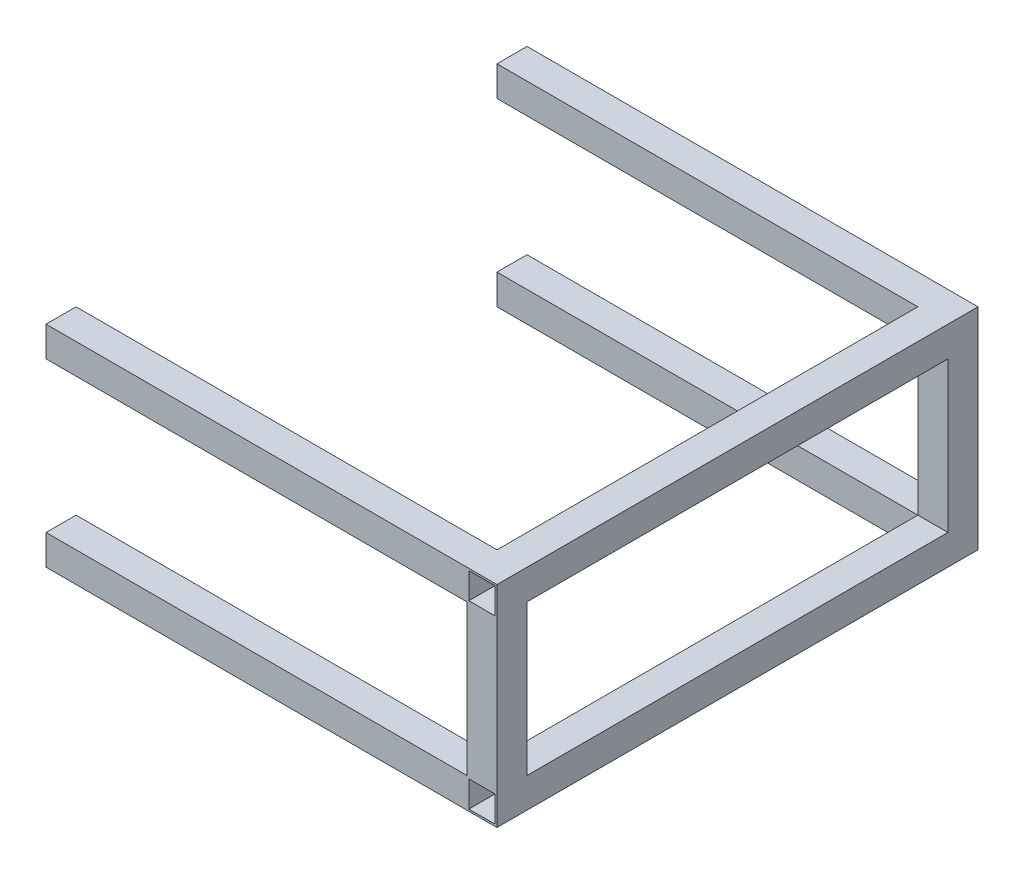
SolidWorks part; units mm, degrees
material "Plain Carbon Steel"
ref_plane "Front Plane" through (0, 0, 0) normal (0, 0, 1) x (1, 0, 0)
ref_plane "Top Plane" through (0, 0, 0) normal (0, 1, 0) x (1, 0, 0)
ref_plane "Right Plane" through (0, 0, 0) normal (1, 0, 0) x (0, 0, -1)
sketch "Sketch1" plane through (0, 0, 0) normal (1, 0, 0) x (0, 0, -1)
  line L1 (-203.2, 88.9) -> (-177.8, 88.9)
  line L2 (-203.2, 88.9) -> (-203.2, 63.5)
  line L3 (-203.2, 63.5) -> (-177.8, 63.5)
  line L4 (-177.8, 88.9) -> (-177.8, 63.5)
  line L5 (-203.2, 88.9) -> (-177.8, 63.5) construction
  line L6 (-203.2, 63.5) -> (-177.8, 88.9) construction
  line L7 (177.8, 88.9) -> (203.2, 88.9)
  line L8 (177.8, 88.9) -> (177.8, 63.5)
  line L9 (177.8, 63.5) -> (203.2, 63.5)
  line L10 (203.2, 88.9) -> (203.2, 63.5)
  line L11 (177.8, 88.9) -> (203.2, 63.5) construction
  line L12 (177.8, 63.5) -> (203.2, 88.9) construction
  line L13 (177.8, -63.5) -> (203.2, -63.5)
  line L14 (177.8, -63.5) -> (177.8, -88.9)
  line L15 (177.8, -88.9) -> (203.2, -88.9)
  line L16 (203.2, -63.5) -> (203.2, -88.9)
  line L17 (177.8, -63.5) -> (203.2, -88.9) construction
  line L18 (177.8, -88.9) -> (203.2, -63.5) construction
  line L19 (-177.8, -63.5) -> (-203.2, -63.5)
  line L20 (-177.8, -63.5) -> (-177.8, -88.9)
  line L21 (-177.8, -88.9) -> (-203.2, -88.9)
  line L22 (-203.2, -63.5) -> (-203.2, -88.9)
  line L23 (-177.8, -63.5) -> (-203.2, -88.9) construction
  line L24 (-177.8, -88.9) -> (-203.2, -63.5) construction
  line L26 (190.5, -76.2) -> (-190.5, -76.2) construction
  line L27 (190.5, -76.2) -> (190.5, 76.2) construction
  line L28 (190.5, 76.2) -> (-190.5, 76.2) construction
  line L29 (-190.5, -76.2) -> (-190.5, 76.2) construction
  line L30 (190.5, -76.2) -> (-190.5, 76.2) construction
  line L31 (190.5, 76.2) -> (-190.5, -76.2) construction
  point P0 (-190.5, 76.2)
  point P5 (190.5, 76.2)
  point P10 (190.5, -76.2)
  point P15 (-190.5, -76.2)
  point P20 (-63.0969, -56.111)
  point P21 (89.3297, -68.4815)
  point P22 (0, 0)
  point P27 (0, 0)
  dimension "D1" = 25.4
  dimension "D2" = 355.6
  dimension "D3" = 152.4
extrude "Extrude-Thin1" add sketch "Sketch1" along normal mid plane 355.6 thin thin type one direction reverse wall 1.651
sketch "Sketch2" plane through (0, 0, 0) normal (0, 0, 1) x (1, 0, 0)
  line L0 (177.8, 88.9) -> (-177.8, 88.9) construction
  line L1 (177.8, 63.5) -> (203.2, 63.5)
  line L2 (177.8, 63.5) -> (177.8, 88.9)
  line L3 (177.8, 88.9) -> (203.2, 88.9)
  line L4 (203.2, 63.5) -> (203.2, 88.9)
  line L5 (177.8, -63.5) -> (-177.8, -63.5) construction
  line L6 (177.8, -88.9) -> (203.2, -88.9)
  line L7 (177.8, -88.9) -> (177.8, -63.5)
  line L8 (177.8, -63.5) -> (203.2, -63.5)
  line L9 (203.2, -88.9) -> (203.2, -63.5)
extrude "Extrude-Thin2" add sketch "Sketch2" along normal up to surface (203.2 mm away) and the other way up to surface (203.2 mm away) thin up to face at (0, 76.2, 203.2) other way up to face at (0, 76.2, -203.2) thin type one direction reverse wall 1.651
sketch "Sketch3" plane through (0, 0, 0) normal (0, 1, 0) x (1, 0, 0)
  line L1 (177.8, 177.8) -> (203.2, 177.8)
  line L2 (177.8, 177.8) -> (177.8, 203.2)
  line L3 (177.8, 203.2) -> (203.2, 203.2)
  line L4 (203.2, 177.8) -> (203.2, 203.2)
  line L5 (177.8, -177.8) -> (203.2, -177.8)
  line L6 (177.8, -177.8) -> (177.8, -203.2)
  line L7 (177.8, -203.2) -> (203.2, -203.2)
  line L8 (203.2, -177.8) -> (203.2, -203.2)
extrude "Extrude-Thin3" add sketch "Sketch3" along normal up to surface and the other way up to surface thin up to face at (6.35, 63.5, 0) thin type one direction reverse wall 1.651
